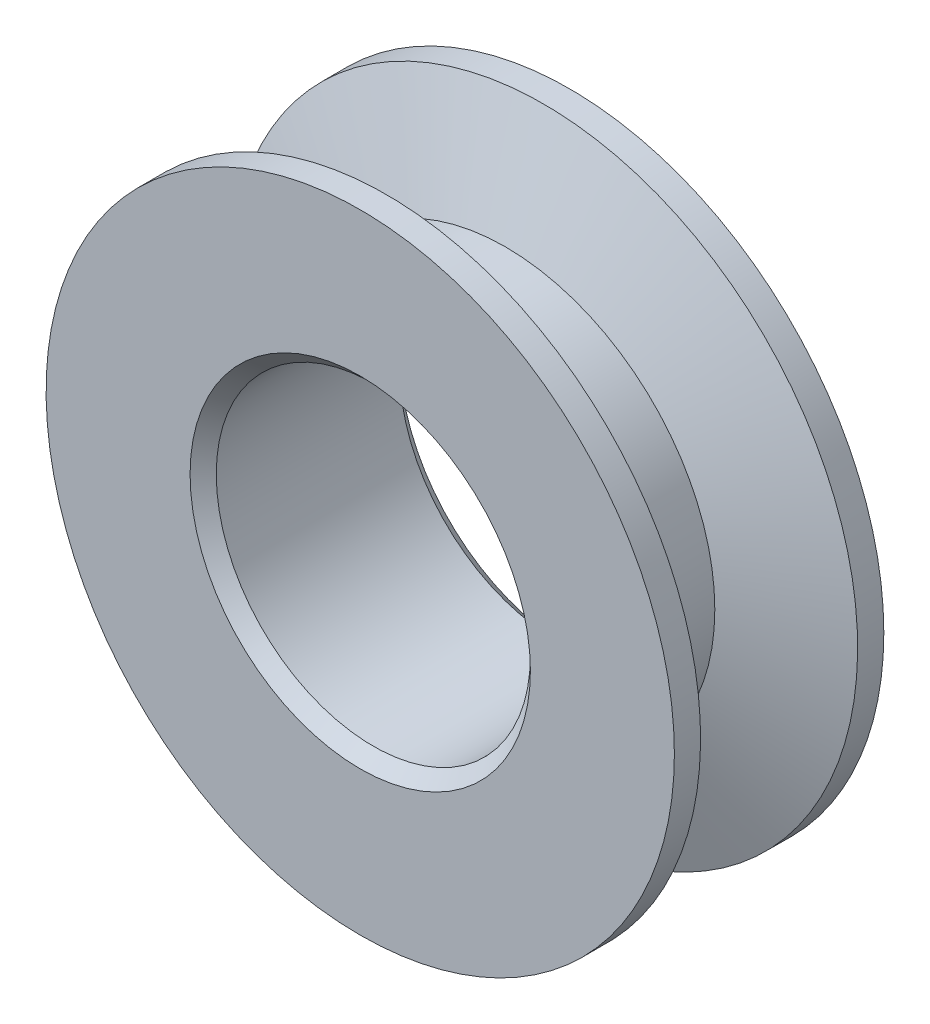
SolidWorks part; units mm, degrees
material "6061-T6 (SS)"
ref_plane "Front Plane" through (0, 0, 0) normal (0, 0, 1) x (1, 0, 0)
ref_plane "Top Plane" through (0, 0, 0) normal (0, 1, 0) x (1, 0, 0)
ref_plane "Right Plane" through (0, 0, 0) normal (1, 0, 0) x (0, 0, -1)
sketch "Sketch1" plane through (0, 0, 0) normal (0, 0, 1) x (1, 0, 0)
  circle A0 centre (0, 0) radius 19.05
  circle A1 centre (0, 0) radius 9.525
  dimension "D1" = 38.1
  dimension "D2" = 19.05
extrude "Extrude1" add sketch "Sketch1" along normal mid plane 12.7
sketch "Sketch2" plane through (0, 0, 0) normal (1, 0, 0) x (0, 0, -1)
  line L0 (-4.7625, 19.05) -> (4.7625, 19.05)
  line L2 (4.7625, 19.05) -> (2.4513, 12.7)
  line L3 (2.4513, 12.7) -> (-2.4513, 12.7)
  line L4 (-2.4513, 12.7) -> (-4.7625, 19.05)
  line L5 (-6.35, 0) -> (6.35, 0) construction
  line L6 (-6.35, 19.05) -> (-6.35, -19.05) construction
  line L7 (6.35, -19.05) -> (6.35, 19.05) construction
  point P2 (0, 19.05)
  point P5 (0, 12.7)
  dimension "D1" = 19.05
  dimension "D2" = 6.35
  dimension "D3" = 9.525
  dimension "D4" = 40
chamfer "Chamfer1" distance 0.7937 angle 45 2 edges at (9.525, 0, -6.35) (9.525, 0, 6.35)
revolve "Cut-Revolve1" cut sketch "Sketch2" angle 360 about L5
